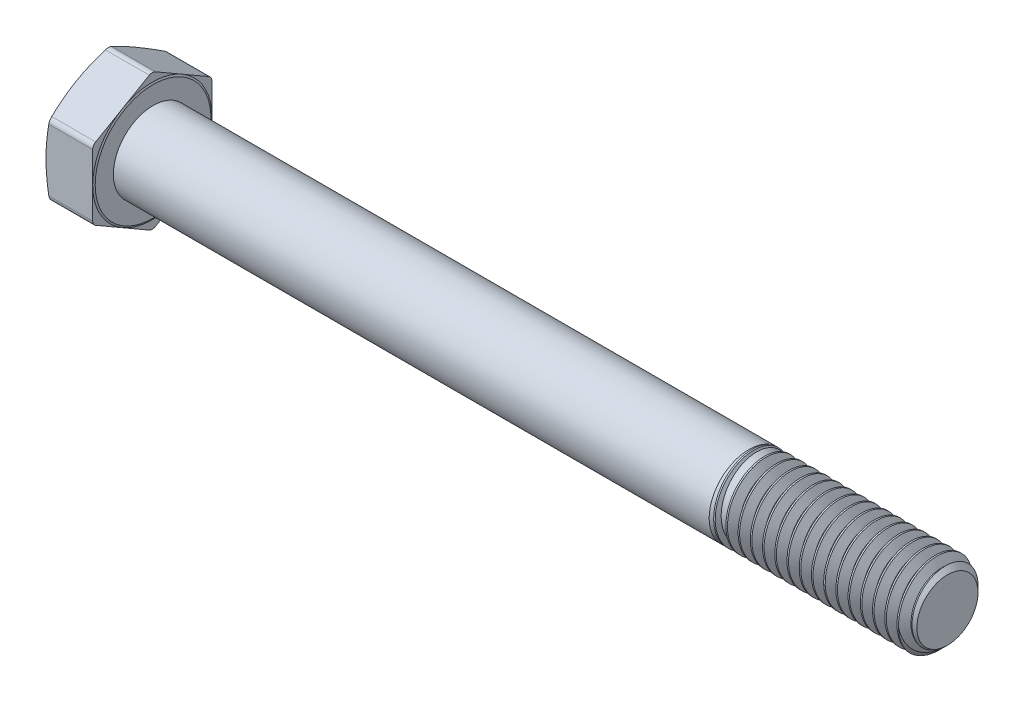
SolidWorks part; units mm, degrees
ref_plane "Front Plane" through (0, 0, 0) normal (0, 0, 1) x (1, 0, 0)
ref_plane "Top Plane" through (0, 0, 0) normal (0, 1, 0) x (1, 0, 0)
ref_plane "Right Plane" through (0, 0, 0) normal (1, 0, 0) x (0, 0, -1)
sketch "Sketch1" plane through (0, 0, 0) normal (0, 0, 1) x (1, 0, 0)
  line L0 (0, 0) -> (127, 0) construction
  line L1 (0, 0) -> (-7.9375, 0) construction
  line L2 (0, 9.525) -> (0, -9.525) construction
  line L3 (-7.9375, 9.525) -> (-7.9375, -9.525) construction
  line L4 (127, 6.35) -> (127, -6.35) construction
  line L5 (95.25, 6.35) -> (95.25, -6.35) construction
  line L8 (125.0462, 6.35) -> (127, 6.35) construction
  point P8 (125.0462, 0)
  point P11 (120.1615, -6.35)
  point P12 (95.25, 0)
  point P15 (6.8385, 0)
  point P16 (88.4115, 0)
  dimension "Head Height" = 7.9375
  dimension "Head Width" = 19.05
  dimension "Length" = 127
  dimension "Thread Size" = 12.7
  dimension "D1" = 6.8385
  dimension "Thread Pitch" = 1.9538
  dimension "Min. Thread Length" = 31.75
  dimension "D2" = 6.8385
  dimension "D3" = 6.8385
sketch "Sketch2" plane through (0, 0, 0) normal (1, 0, 0) x (0, 0, -1)
  circle A0 centre (0, 0) radius 6.35
extrude "Boss-Extrude1" add sketch "Sketch2" along normal up to vertex (127 mm away) up to point (127, 6.35, 0)
sketch "Sketch3" plane through (0, 0, 0) normal (-1, 0, 0) x (0, 0, 1)
  line L0 (0, 10.9985) -> (0, 0) construction
  line L1 (0, 10.9985) -> (-9.525, 5.4993)
  line L2 (-9.525, 5.4993) -> (-9.525, -5.4993)
  line L3 (-9.525, -5.4993) -> (0, -10.9985)
  line L4 (0, -10.9985) -> (9.525, -5.4993)
  line L5 (9.525, -5.4993) -> (9.525, 5.4993)
  line L6 (9.525, 5.4993) -> (0, 10.9985)
  circle A0 centre (0, 0) radius 9.525 construction
extrude "Boss-Extrude2" add sketch "Sketch3" along normal up to vertex (7.9375 mm away) up to point (-7.9375, 9.525, 0)
sketch "Sketch5" plane through (-7.9375, 0, 0) normal (-1, 0, 0) x (0, 0, 1)
  circle A0 centre (0, 0) radius 9.525 construction
  circle A1 centre (0, 0) radius 9.525 construction
  circle A2 centre (0, 0) radius 8.5725
  dimension "D1" = 0.9525
extrude "Cut-Extrude1" cut sketch "Sketch5" against normal up to vertex (7.9375 mm away) draft 70 flip side to cut up to point (0, 0, 0)
sketch "Sketch11" plane through (-7.9375, 0, 0) normal (-1, 0, 0) x (0, 0, 1)
  line L0 (0, 6.7627) -> (0, 3.7148) construction
  line L1 (0.381, 6.7627) -> (0.381, 3.7148)
  line L2 (-0.381, 6.7627) -> (-0.381, 3.7148)
  arc A0 (0.381, 6.7627) -> (-0.381, 6.7627) centre (0, 6.7627) ccw
  arc A1 (-0.381, 3.7148) -> (0.381, 3.7148) centre (0, 3.7148) ccw
  circle A2 centre (0, 0) radius 7.1438 construction
  circle A3 centre (0, 0) radius 3.3338 construction
  point P3 (0, 5.2388)
  dimension "D1" = 14.2875
  dimension "D2" = 6.6675
  dimension "D3" = 0.762
extrude "Boss-Extrude5" add sketch "Sketch11" along normal blind 0.0635
fillet "Fillet5" radius 0.0635 4 edges at (-8.001, 5.2388, 0.381) (-8.001, 3.3338, 0) (-8.001, 5.2388, -0.381) (-8.001, 7.1437, 0)
fillet "Fillet6" radius 0.0635 4 edges at (-7.9375, 3.3338, 0) (-7.9375, 5.2388, -0.381) (-7.9375, 7.1437, 0) (-7.9375, 5.2388, 0.381)
pattern_circular "CirPattern1" count 6 over 360 about axis through (0, 0, 0) along (-1, 0, 0) of "Boss-Extrude5", "Fillet5", "Fillet6" reverse direction yes
fillet "Fillet7" radius 0.9525 6 edges at (-3.5272, -10.9985, 0) (-3.5272, -5.4993, -9.525) (-3.5272, 5.4993, -9.525) (-3.5272, 10.9985, 0) (-3.5272, -5.4993, 9.525) (-3.5272, 5.4993, 9.525)
chamfer "Chamfer1" distance 1.4654 angle 45 1 edges at (127, 0, -6.35)
sketch "Sketch15" plane through (0, 0, 0) normal (0, 0, 1) x (1, 0, 0)
  line L0 (0, 9.2526) -> (-0.127, 9.525)
  line L1 (0, 9.525) -> (0, -9.525) construction
  line L2 (-0.127, 9.525) -> (-0.127, 10.9985)
  line L3 (-0.127, 10.9985) -> (0, 10.9985)
  line L4 (0, 10.9985) -> (0, 9.2526)
  line L5 (0, 5.4993) -> (0, 10.9985) construction
  dimension "D1" = 25
  dimension "D2" = 0.127
revolve "Cut-Revolve1" cut sketch "Sketch15" angle 360 about L0
sketch "Reference Sketch1" plane through (0, 0, 0) normal (1, 0, 0) x (0, 0, -1)
  line L1 (0, 10.9985) -> (-9.525, 5.4993)
  line L2 (-9.525, 5.4993) -> (-9.525, -5.4993)
  line L3 (-9.525, -5.4993) -> (0, -10.9985)
  line L4 (0, -10.9985) -> (9.525, -5.4993)
  line L5 (9.525, -5.4993) -> (9.525, 5.4993)
  line L6 (9.525, 5.4993) -> (0, 10.9985)
  circle A0 centre (0, 0) radius 9.525 construction
  circle A1 centre (0, 0) radius 9.525
sketch "Sketch12" plane through (127, 0, 0) normal (1, 0, 0) x (0, 0, -1)
  circle A1 centre (0, 0) radius 6.35
ref_plane "Plane2" through (95.25, 0, 0) normal (1, 0, 0) x (0, 0, -1)
split "Split1" trim tools "Plane2" bodies to split 126 116 resulting bodies 118 119
curve "Helix/Spiral2" pitch 1.9538 height 33.7038 radius 6.35 centre (127, 0, 0) axis (-1, 0, 0) start towards (0, 1, 0) parameters "Pitch"=1.9538
sketch "Sketch13" plane through (0, 0, 0) normal (0, 0, 1) x (1, 0, 0)
  line L0 (126.8779, 6.5615) -> (127.8548, 4.8694) construction
  line L1 (127.8548, 4.8694) -> (128.8317, 6.5615) construction
  line L2 (128.8317, 6.5615) -> (126.8779, 6.5615) construction
  line L3 (127.8548, 4.8694) -> (127.8548, 5.0809) construction
  line L4 (127, 6.35) -> (128.7096, 6.35)
  line L5 (127.8548, 6.35) -> (127.8548, 6.5615) construction
  line L6 (128.7096, 6.35) -> (127.9769, 5.0809)
  line L7 (127.9769, 5.0809) -> (127.7327, 5.0809)
  line L8 (127.7327, 5.0809) -> (127, 6.35)
  line L9 (125.0462, 6.35) -> (127, 6.35) construction
  dimension "D1" = 0.2442
sweep "Cut-Sweep1" cut profiles "Sketch13" path "Helix/Spiral2" align with end faces yes
sketch "Sketch14" plane through (95.25, 0, 0) normal (1, 0, 0) x (0, 0, -1)
  circle A1 centre (0, 0) radius 6.35
  circle A2 centre (0, 0) radius 6.35
  dimension "D1" = 0
extrude "Boss-Extrude4" add sketch "Sketch14" along normal through all draft 25
equation "\"D1@Sketch11\"=\"Head Width@Sketch1\" * 0.75"
equation "\"D2@Sketch11\"=\"Head Width@Sketch1\"*0.35"
equation "\"D3@Sketch11\"=\"Head Width@Sketch1\" * .04"
equation "\"D3@Helix/Spiral2\"=\"Min. Thread Length@Sketch1\" + \"Thread Pitch@Sketch1\""
equation "\"Pitch@Helix/Spiral2\"=\"Thread Pitch@Sketch1\""
equation "\"D1@Sketch13\"=\"Thread Pitch@Sketch1\"*0.125"
equation "\"D1@Sketch5\"=\"Head Width@Sketch1\"*0.05"
equation "\"D1@Sketch1\"=\"Thread Pitch@Sketch1\"*3.5"
equation "\"D1@Chamfer1\"=\"Thread Pitch@Sketch1\"*0.750"
equation "\"D1@Fillet7\"=\"Head Width@Sketch1\"*0.05"
equation "\"DC1@Fillet\"=\"Head Width@Sketch1\"*0.005"
equation "\"D1@Fillet10\"=\"Head Width@Sketch1\"*0.01"
equation "\"D2@Sketch1\"=\"D1@Sketch1\""
equation "\"D3@Sketch1\"=\"D1@Sketch1\""
equation "\"D1@Fillet4\"=\"Thread Size@Sketch1\"*0.05"
